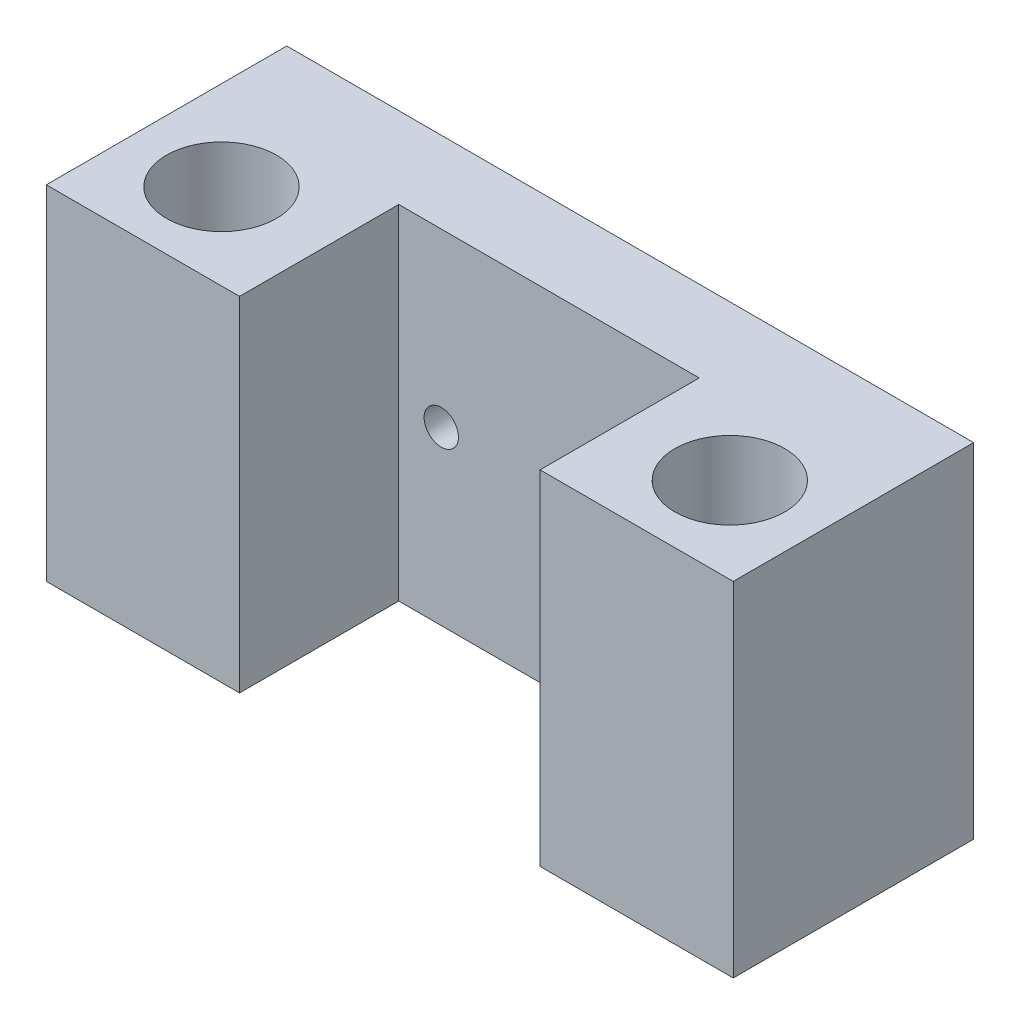
SolidWorks part; units mm, degrees
ref_plane "Front Plane" through (0, 0, 0) normal (0, 0, 1) x (1, 0, 0)
ref_plane "Top Plane" through (0, 0, 0) normal (0, 1, 0) x (1, 0, 0)
ref_plane "Right Plane" through (0, 0, 0) normal (1, 0, 0) x (0, 0, -1)
sketch "Sketch3" plane through (0, 0, 0) normal (0, 0, 1) x (1, 0, 0)
  line L1 (-50, -25) -> (50, -25)
  line L2 (-50, -25) -> (-50, 25)
  line L3 (-50, 25) -> (50, 25)
  line L4 (50, -25) -> (50, 25)
  line L5 (-50, -25) -> (50, 25) construction
  line L6 (-50, 25) -> (50, -25) construction
  point P0 (0, 0)
extrude "Boss-Extrude1" add sketch "Sketch3" along normal blind 25
sketch "Sketch5" plane through (0, 25, 0) normal (0, 1, 0) x (1, 0, 0)
  line L11 (-21.873, -25) -> (-21.873, -1.8248)
  line L12 (50, -25) -> (-50, -25) construction
  line L16 (-21.873, -1.8248) -> (21.873, -1.8248)
  line L17 (21.873, -1.8248) -> (21.873, -25)
  line L18 (21.873, -25) -> (-21.873, -25)
  circle A1 centre (37, -12.5) radius 8
  circle A2 centre (-37, -12.5) radius 8
  point P12 (0, -5)
  point P16 (0, -12.5)
extrude "Cut-Extrude1" cut sketch "Sketch5" against normal through all
sketch "Sketch7" plane through (0, 0, 0) normal (0, 0, -1) x (-1, 0, 0)
  circle A0 centre (32.5, 9.25) radius 2.5
  circle A1 centre (32.5, -9.25) radius 2.5
  circle A2 centre (-32.5, -9.25) radius 2.5
  circle A3 centre (-32.5, 9.25) radius 2.5
  point P8 (0, 0)
  point P11 (32.5, 0)
  point P14 (0, 0)
  point P16 (0, 0)
  point P23 (0, 0)
  dimension "D1" = 5
  dimension "D2" = 18.5
extrude "Cut-Extrude4" cut sketch "Sketch7" against normal blind 10
sketch "Sketch8" plane through (0, 0, 0) normal (0, 0, -1) x (-1, 0, 0)
  line L0 (-50, 25) -> (50, 25)
  line L1 (50, 25) -> (50, -25)
  line L2 (50, -25) -> (-50, -25)
  line L3 (-50, -25) -> (-50, 25)
  circle A0 centre (-32.5, 9.25) radius 2.5
  circle A1 centre (-32.5, -9.25) radius 2.5
  circle A2 centre (32.5, -9.25) radius 2.5
  circle A3 centre (32.5, 9.25) radius 2.5
extrude "Boss-Extrude2" add sketch "Sketch8" along normal blind 10
sketch "Sketch9" plane through (0, 0, 1.8248) normal (0, 0, 1) x (1, 0, 0)
  circle A0 centre (-15.68, 0) radius 2.5
  circle A1 centre (15.68, 0) radius 2.5
  point P8 (0, 0)
extrude "Cut-Extrude5" cut sketch "Sketch9" against normal through all
